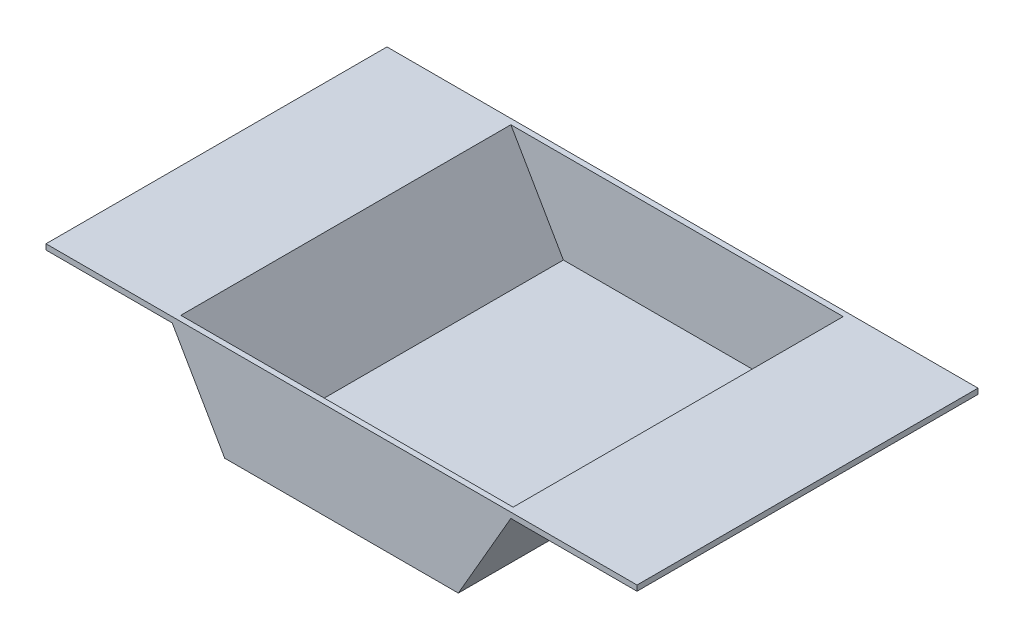
SolidWorks part; units mm, degrees
ref_plane "Front Plane" through (0, 0, 0) normal (0, 0, 1) x (1, 0, 0)
ref_plane "Top Plane" through (0, 0, 0) normal (0, 1, 0) x (1, 0, 0)
ref_plane "Right Plane" through (0, 0, 0) normal (1, 0, 0) x (0, 0, -1)
sketch "Sketch2" plane through (0, 0, 0) normal (0, 0, 1) x (1, 0, 0)
  line L2 (0, -1000) -> (0, 0) construction
  line L4 (-330.2, 101.6) -> (-185.6588, 101.6)
  line L5 (185.6588, 101.6) -> (330.2, 101.6)
  line L6 (-330.2, 95.504) -> (-189.1783, 95.504)
  line L7 (-130.5195, -6.096) -> (-189.1783, 95.504)
  line L8 (-130.5195, -6.096) -> (130.5195, -6.096)
  line L9 (130.5195, -6.096) -> (189.1783, 95.504)
  line L10 (189.1783, 95.504) -> (330.2, 95.504)
  line L11 (-330.2, 101.6) -> (-330.2, 95.504)
  line L12 (330.2, 101.6) -> (330.2, 95.504)
  line L13 (-185.6588, 101.6) -> (185.6588, 101.6)
  line L14 (-127, 0) -> (127, 0) construction
  line L15 (-127, 0) -> (-185.6588, 101.6) construction
  line L16 (0, 101.6) -> (0, 50000) construction
  line L17 (127, 0) -> (185.6588, 101.6) construction
  point P8 (0, 0)
  point P11 (0, 101.6)
  dimension "D4" = 660.4
  dimension "D5" = 6.096
extrude "Boss-Extrude2" add sketch "Sketch2" along normal blind 381
shell "Shell1" thickness 6.096 removed face at (0, 101.6, 190.5)
